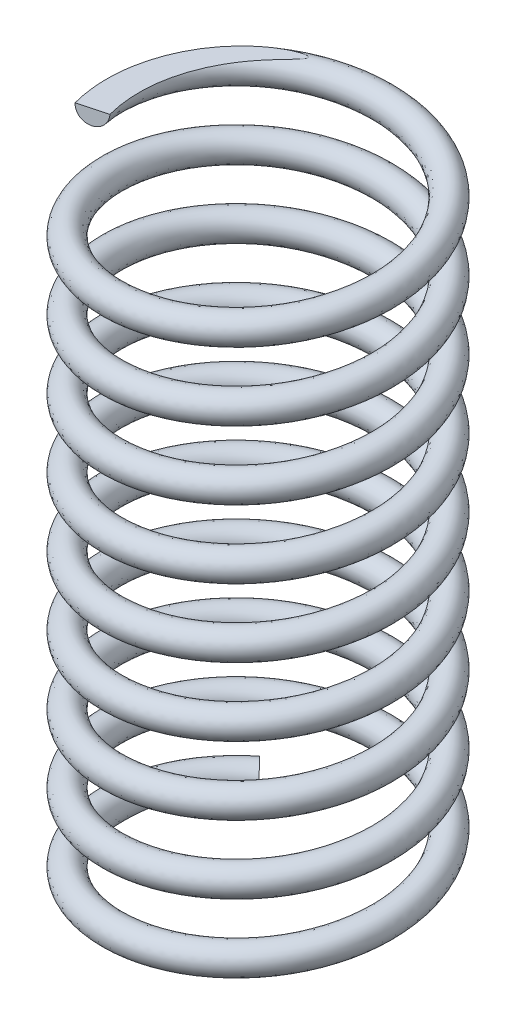
SolidWorks part; units mm, degrees
ref_plane "前视基准面" through (0, 0, 0) normal (0, 0, 1) x (1, 0, 0)
ref_plane "上视基准面" through (0, 0, 0) normal (0, 1, 0) x (1, 0, 0)
ref_plane "右视基准面" through (0, 0, 0) normal (1, 0, 0) x (0, 0, -1)
sketch "草图1" plane through (0, 0, 0) normal (0, 1, 0) x (1, 0, 0)
  circle A0 centre (0, 0) radius 4.75
  dimension "D1" = 9.5
curve "螺旋线/涡状线1" pitch 2.4 height 22 radius 4.75 centre (0, 0, 0) axis (0, 1, 0) start towards (0, 0, 1)
sweep "扫描1" add path "螺旋线/涡状线1" circular profile diameter 1 parameters "D3"=1
sketch "草图10" plane through (0, 0, 0) normal (0, 0, 1) x (1, 0, 0)
  line L0 (-6.043, 0) -> (9.8816, 0)
  line L1 (6.0119, 0) -> (-6.0119, 0) construction
extrude "切除-拉伸1" cut sketch "草图10" against normal through all and the other way through all flip side to cut
sketch "草图11" plane through (0, 0, 0) normal (0, 0, 1) x (1, 0, 0)
  line L0 (9.4924, 22) -> (-9.5424, 22)
  line L1 (6.0119, 0) -> (-6.0119, 0) construction
  dimension "D1" = 22
extrude "切除-拉伸2" cut sketch "草图11" against normal through all and the other way through all flip side to cut
